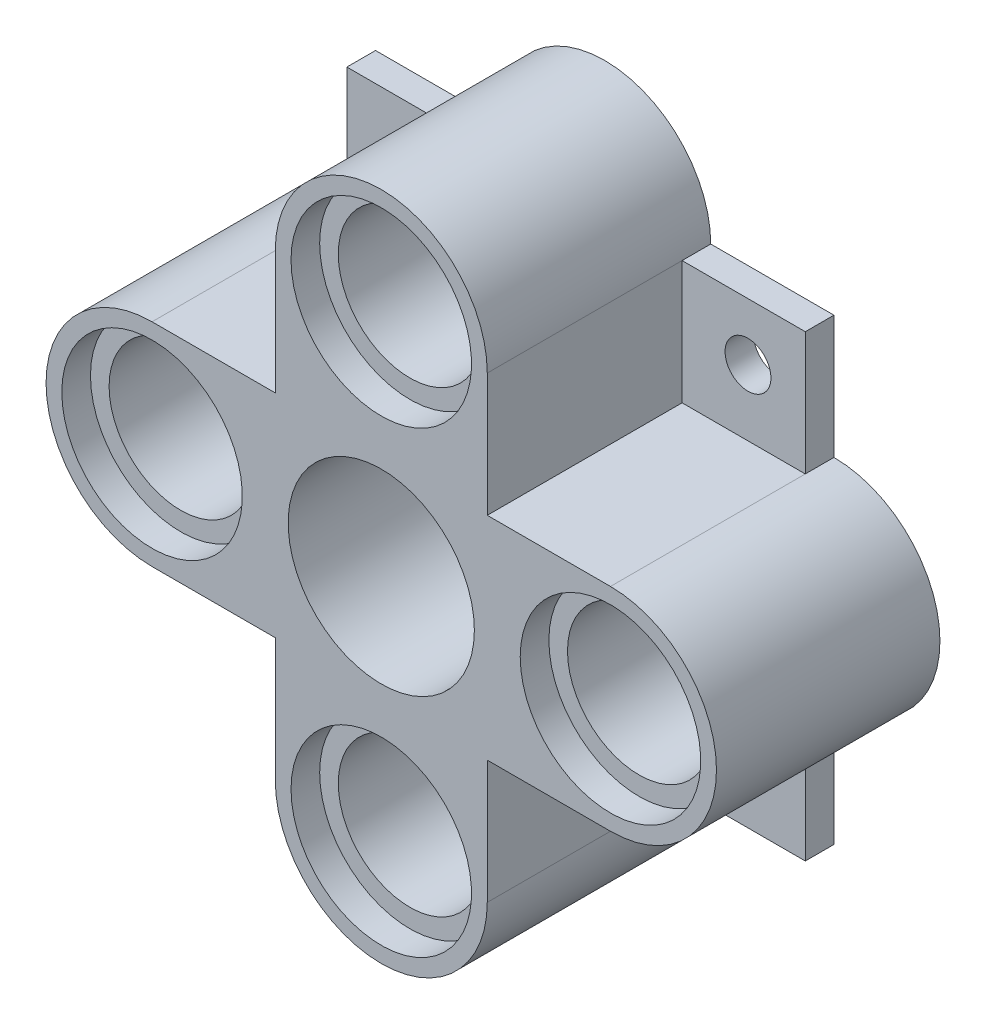
SolidWorks part; units mm, degrees
ref_plane "前视基准面" through (0, 0, 0) normal (0, 0, 1) x (1, 0, 0)
ref_plane "上视基准面" through (0, 0, 0) normal (0, 1, 0) x (1, 0, 0)
ref_plane "右视基准面" through (0, 0, 0) normal (1, 0, 0) x (0, 0, -1)
other "Configuration Table"
sketch "草图2" plane through (0, 0, 0) normal (0, 0, 1) x (1, 0, 0)
  line L0 (-8, 0) -> (8, 0) construction
  line L2 (-11.7, -3.7) -> (11.7, -3.7)
  line L3 (-11.7, -3.7) -> (-11.7, 3.7)
  line L4 (-11.7, 3.7) -> (11.7, 3.7)
  line L5 (11.7, -3.7) -> (11.7, 3.7)
  line L6 (-11.7, -3.7) -> (11.7, 3.7) construction
  line L7 (-11.7, 3.7) -> (11.7, -3.7) construction
  line L8 (-3.7, 11.7) -> (3.7, 11.7)
  line L9 (-3.7, 11.7) -> (-3.7, -11.7)
  line L10 (-3.7, -11.7) -> (3.7, -11.7)
  line L11 (3.7, 11.7) -> (3.7, -11.7)
  line L12 (-3.7, 11.7) -> (3.7, -11.7) construction
  line L13 (-3.7, -11.7) -> (3.7, 11.7) construction
  circle A0 centre (0, 0) radius 3.25
  circle A1 centre (-8, 0) radius 2.5
  circle A2 centre (8, 0) radius 2.5
  circle A3 centre (8, 0) radius 3.15
  circle A4 centre (-8, 0) radius 3.15
  circle A5 centre (-8, 0) radius 3.7
  circle A6 centre (8, 0) radius 3.7
  circle A7 centre (0, 8) radius 2.5
  circle A8 centre (0, 8) radius 3.15
  circle A9 centre (0, 8) radius 3.7
  circle A10 centre (0, -8) radius 2.5
  circle A11 centre (0, -8) radius 3.15
  circle A12 centre (0, -8) radius 3.7
  point P15 (0, 0)
  dimension "D2" = 5
  dimension "D3" = 6.5
  dimension "D4" = 6.3
  dimension "D1" = 8
  dimension "D5" = 7.4
extrude "凸台-拉伸1" add sketch "草图2" along normal blind 7.8 contours L4 L5 L2 L3 | L8 L11 L10 L9
sketch "草图3" plane through (0, 0, 0) normal (0, 0, -1) x (-1, 0, 0)
  line L1 (-8, 8) -> (8, 8)
  line L2 (-8, 8) -> (-8, -8)
  line L3 (-8, -8) -> (8, -8)
  line L4 (8, 8) -> (8, -8)
  line L5 (-8, 8) -> (8, -8) construction
  line L6 (-8, -8) -> (8, 8) construction
  point P0 (0, 0)
  point P5 (0, 0)
  point P7 (0, 0)
  point P12 (0, 0)
  point P13 (0, 0)
  point P14 (0, 0)
  dimension "D1" = 16
  dimension "D2" = 16
extrude "凸台-拉伸2" add sketch "草图3" against normal blind 1 contours L1 L4 L3 L2
extrude "切除-拉伸3" cut sketch "草图2<6>" along normal through all contours A9 L8 L9 | A9 L11 L8 | A6 L5 L4 | A6 L2 L5 | A12 L10 L11 | A12 L9 L10 | A5 L3 L2 | A5 L4 L3 | A7 | A1 | A0 | A2 | A10 region at (-10.8735, -2.8735, 0) region at (-10.8735, 2.8735, 0) region at (-2.8735, -10.8735, 0) region at (10.8735, -2.8735, 0) region at (2.8735, -10.8735, 0) region at (-2.8735, 10.8735, 0) region at (10.8735, 2.8735, 0) region at (2.8735, 10.8735, 0)
sketch "草图2<6>" plane through (0, 0, 0) normal (0, 0, 1) x (1, 0, 0) same geometry as "草图2"
extrude "切除-拉伸1" cut sketch "草图2<3>" along normal blind 1 contours A4 | A8 | A3 | A11
sketch "草图2<3>" plane through (0, 0, 0) normal (0, 0, 1) x (1, 0, 0) same geometry as "草图2"
extrude "切除-拉伸2" cut sketch "草图2<5>" against normal blind 1 from surface contours A4 | A11 | A3 | A8 starting at face at (-5.5, 0, 7.8)
sketch "草图2<5>" plane through (0, 0, 0) normal (0, 0, 1) x (1, 0, 0) same geometry as "草图2"
sketch "草图4" plane through (0, 0, 1) normal (0, 0, 1) x (1, 0, 0)
  line L0 (-8, 8) -> (-3.7, 3.7) construction
  line L1 (3.7, -3.7) -> (8, -8) construction
  line L2 (-3.7, 8) -> (-8, 8) construction
  line L5 (8, -8) -> (3.7, -8) construction
  circle A0 centre (-6, 6) radius 0.8
  circle A1 centre (6, 6) radius 0.8
  circle A2 centre (-6, -6) radius 0.8
  circle A3 centre (6, -6) radius 0.8
  point P18 (0, 0)
  point P19 (0, 0)
  dimension "D1" = 1.6
  dimension "D2" = 2
  dimension "D3" = 2
extrude "切除-拉伸4" cut sketch "草图4" against normal through all contours A0 | A1 | A3 | A2
